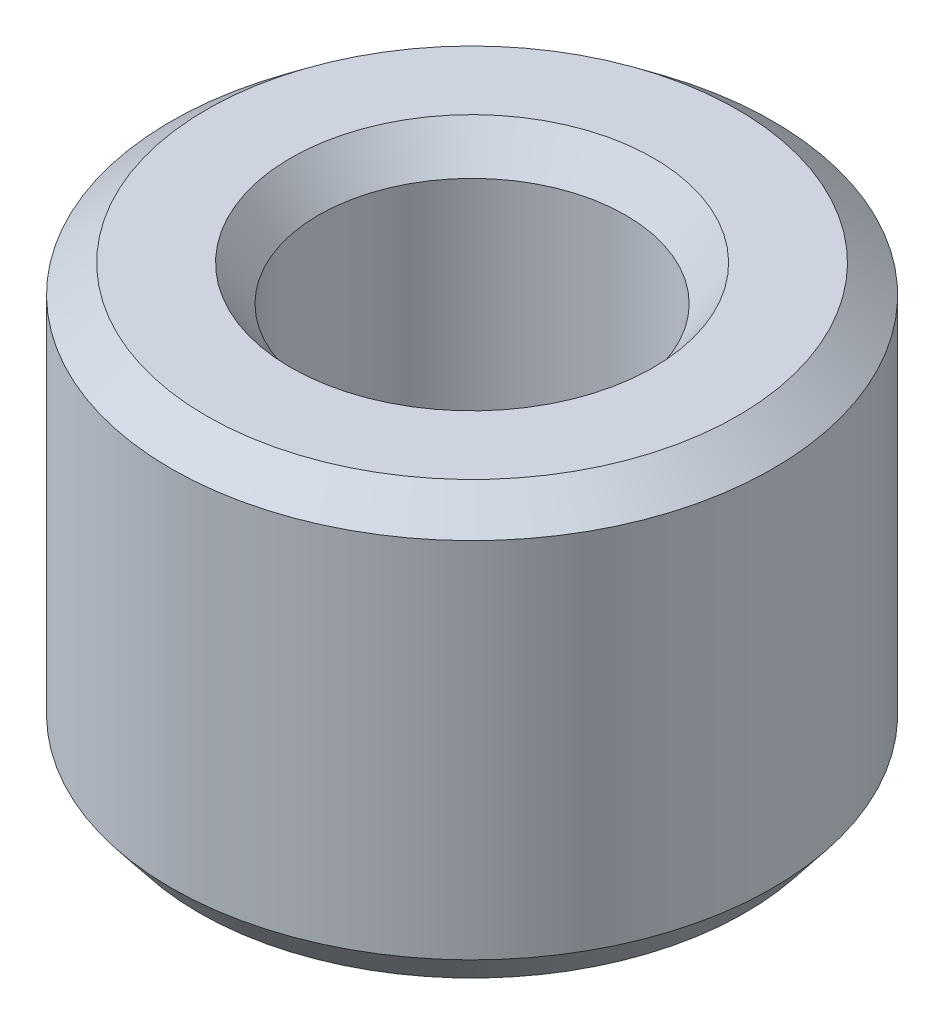
SolidWorks part; units mm, degrees
ref_plane "Front Plane" through (0, 0, 0) normal (0, 0, 1) x (1, 0, 0)
ref_plane "Top Plane" through (0, 0, 0) normal (0, 1, 0) x (1, 0, 0)
ref_plane "Right Plane" through (0, 0, 0) normal (1, 0, 0) x (0, 0, -1)
sketch "Sketch1" plane through (0, 0, 0) normal (0, 1, 0) x (1, 0, 0)
  circle A0 centre (0, 0) radius 30
  dimension "SLEEVE_OD" = 60
extrude "Boss-Extrude1" add sketch "Sketch1" along normal blind 42.5115
sketch "Sketch2" plane through (0, 0, 0) normal (0, 1, 0) x (1, 0, 0)
  circle A0 centre (0, 0) radius 15.3049
  dimension "BORE_D" = 30.6099
extrude "Cut-Extrude1" cut sketch "Sketch2" along normal through all
chamfer "Chamfer1" distance 2.7809 angle 51.812 4 edges at (0, 42.5115, 15.3049) (0, 0, 15.3049) (0, 0, 30) (0, 42.5115, 30) first distance on face at (0, 42.5115, 15.3049) first distance on face at (0, 0, 15.3049) first distance on face at (0, 42.5115, 30)
